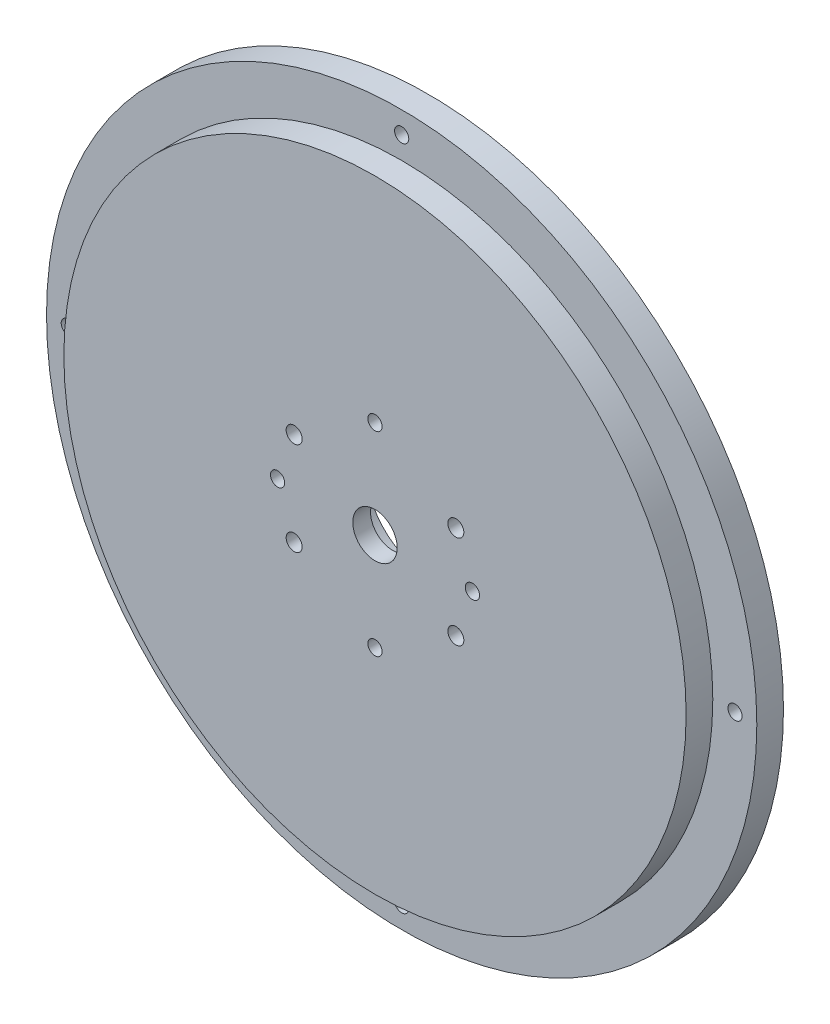
SolidWorks part; units mm, degrees
ref_plane "前视基准面" through (0, 0, 0) normal (0, 0, 1) x (1, 0, 0)
ref_plane "上视基准面" through (0, 0, 0) normal (0, 1, 0) x (1, 0, 0)
ref_plane "右视基准面" through (0, 0, 0) normal (1, 0, 0) x (0, 0, -1)
other "Configuration Table"
sketch "草图1" plane through (0, 0, 0) normal (0, 0, 1) x (1, 0, 0)
  circle A0 centre (0, 0) radius 79.9
  circle A1 centre (0, 0) radius 70
  dimension "D1" = 159.8
  dimension "D2" = 140
extrude "凸台-拉伸1" add sketch "草图1" along normal blind 12 contours A1
sketch "草图2" plane through (0, 0, 0) normal (0, 0, 1) x (1, 0, 0)
  circle A0 centre (0, 0) radius 79.9
  dimension "D1" = 159.8
extrude "凸台-拉伸2" add sketch "草图2" along normal blind 6 contours A0
sketch "草图3" plane through (0, 0, 0) normal (0, 0, 1) x (1, 0, 0)
  circle A0 centre (-75, 0) radius 1.6
  circle A1 centre (75, 0) radius 1.6
  circle A2 centre (0, -75) radius 1.6
  circle A3 centre (0, 75) radius 1.6
  dimension "D1" = 3.2
  dimension "D2" = 3.2
  dimension "D3" = 3.2
  dimension "D4" = 3.2
  dimension "D5" = 75
  dimension "D6" = 75
  dimension "D7" = 75
  dimension "D8" = 75
extrude "切除-拉伸1" cut sketch "草图3" along normal blind 10
sketch "草图4" plane through (0, 0, 0) normal (0, 0, -1) x (-1, 0, 0)
  line L0 (0, 0) -> (-21.9203, 0) construction
  line L1 (0, 0) -> (0, 21.9203) construction
  line L2 (0, 0) -> (21.9203, 0) construction
  line L3 (0, 0) -> (0, -21.9203) construction
  circle A0 centre (-21.9203, 0) radius 1.6
  circle A1 centre (0, 21.9203) radius 1.6
  circle A2 centre (21.9203, 0) radius 1.6
  circle A3 centre (0, -21.9203) radius 1.6
  dimension "D1" = 3.2
  dimension "D2" = 21.9203
  dimension "D4" = 90
  dimension "D5" = 21.9203
  dimension "D3" = 4
extrude "切除-拉伸2" cut sketch "草图4" against normal blind 20 contours A3
extrude "切除-拉伸3" cut sketch "草图4<5>" against normal blind 20
sketch "草图4<5>" plane through (0, 0, 0) normal (0, 0, -1) x (-1, 0, 0) same geometry as "草图4"
sketch "草图6" plane through (0, 0, 0) normal (0, 0, -1) x (-1, 0, 0)
  circle A0 centre (0, 0) radius 5
  dimension "D1" = 10
extrude "切除-拉伸5" cut sketch "草图6" against normal blind 20
sketch "草图7" plane through (0, 0, 0) normal (0, 0, -1) x (-1, 0, 0)
  line L0 (0, 0) -> (-18.1865, 10.5)
  line L1 (0, 0) -> (0, 75)
  line L2 (0, 0) -> (0, 21)
  line L3 (0, 0) -> (18.1865, 10.5)
  line L4 (0, 0) -> (18.1865, -10.5)
  line L5 (0, 0) -> (0, -21)
  line L6 (0, 0) -> (-18.1865, -10.5)
  circle A0 centre (-18.1865, 10.5) radius 1.8
  circle A5 centre (18.1865, 10.5) radius 1.8
  circle A6 centre (18.1865, -10.5) radius 1.8
  circle A8 centre (-18.1865, -10.5) radius 1.8
  circle A9 centre (0, 21) radius 1.8 [skipped]
  circle A10 centre (0, -21) radius 1.8 [skipped]
  point P15 (0, 0)
  point P20 (0, 0)
  dimension "D3" = 3.6
  dimension "D1" = 60
  dimension "D2" = 21
  dimension "D4" = 6
extrude "切除-拉伸8" cut sketch "草图7" against normal blind 30 contours A0 | A5 | A6 | A8
sketch "草图10" plane through (0, 0, 0) normal (0, 0, -1) x (-1, 0, 0)
  circle A0 centre (0, 0) radius 14
  dimension "D1" = 28
extrude "切除-拉伸9" cut sketch "草图10" against normal blind 8 contours A0
